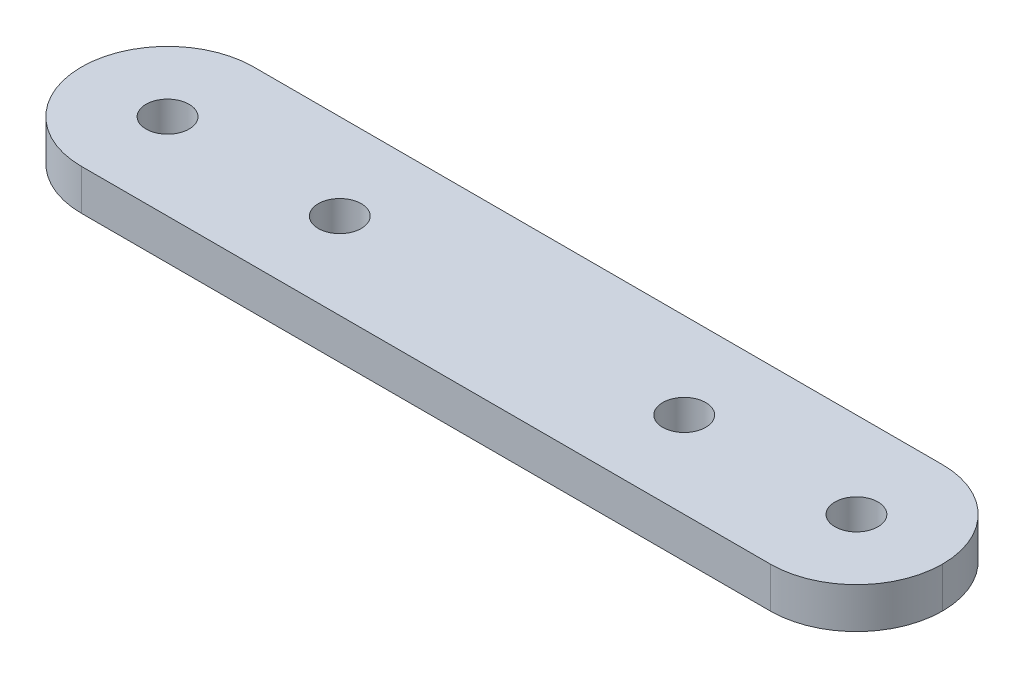
SolidWorks part; units mm, degrees
ref_plane "Front Plane" through (0, 0, 0) normal (0, 0, 1) x (1, 0, 0)
ref_plane "Top Plane" through (0, 0, 0) normal (0, 1, 0) x (1, 0, 0)
ref_plane "Right Plane" through (0, 0, 0) normal (1, 0, 0) x (0, 0, -1)
sketch "Sketch1" plane through (0, 0, 0) normal (0, 1, 0) x (1, 0, 0)
  line L1 (-31.75, -6.35) -> (31.75, -6.35)
  line L2 (-31.75, -6.35) -> (-31.75, 6.35)
  line L3 (-31.75, 6.35) -> (31.75, 6.35)
  line L4 (31.75, -6.35) -> (31.75, 6.35)
  line L5 (-31.75, -6.35) -> (31.75, 6.35) construction
  line L6 (-31.75, 6.35) -> (31.75, -6.35) construction
  circle A0 centre (-12.7, 0) radius 1.5875
  circle A1 centre (12.7, 0) radius 1.5875
  circle A2 centre (25.4, 0) radius 1.5875
  circle A3 centre (-25.4, 0) radius 1.5875
  point P0 (0, 0)
  point P14 (0, 0)
  dimension "D3" = 25.4
  dimension "D5" = 3.175
  dimension "D6" = 3.175
  dimension "D7" = 3.175
  dimension "D8" = 3.175
  dimension "D1" = 12.7
  dimension "D2" = 63.5
  dimension "D4" = 12.7
  dimension "D9" = 12.7
  dimension "D10" = 12.7
extrude "Boss-Extrude1" add sketch "Sketch1" along normal blind 3
fillet "Fillet1" radius 6.35 4 edges at (-31.75, 1.5, -6.35) (-31.75, 1.5, 6.35) (31.75, 1.5, -6.35) (31.75, 1.5, 6.35)
